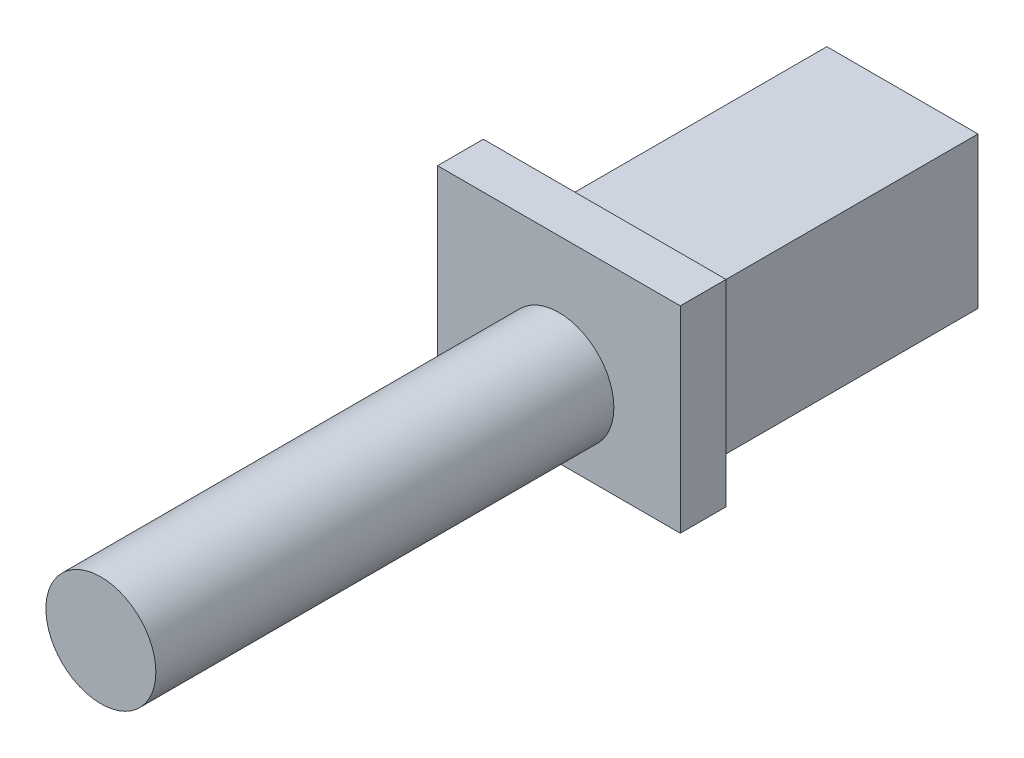
SolidWorks part; units mm, degrees
ref_plane "Front" through (0, 0, 0) normal (0, 0, 1) x (1, 0, 0)
ref_plane "Top" through (0, 0, 0) normal (0, 1, 0) x (1, 0, 0)
ref_plane "Right" through (0, 0, 0) normal (1, 0, 0) x (0, 0, -1)
sketch "Sketch3" plane through (0, 0, 0) normal (0, 0, 1) x (1, 0, 0)
  line L0 (-3.3, -3.3) -> (-5.3, -3.3)
  line L1 (-3.3, 3.3) -> (3.3, 3.3)
  line L2 (-3.3, 3.3) -> (-3.3, -3.3)
  line L3 (-3.3, -3.3) -> (3.3, -3.3)
  line L4 (3.3, 3.3) -> (3.3, -3.3)
  line L5 (-3.3, 3.3) -> (3.3, -3.3) construction
  line L6 (-3.3, -3.3) -> (3.3, 3.3) construction
  line L7 (-5.3, -3.3) -> (-5.3, 5.3)
  line L8 (-5.3, 5.3) -> (5.3, 5.3)
  line L9 (5.3, 5.3) -> (5.3, -3.3)
  line L10 (3.3, -3.3) -> (5.3, -3.3)
  circle A0 centre (0, 0) radius 2.4
  point P0 (0, 0)
  dimension "D2" = 4.8
  dimension "D1" = 6.6
  dimension "D3" = 2
  dimension "D4" = 2
  dimension "D5" = 2
extrude "Boss-Extrude1" add sketch "Sketch3" along normal blind 20 contours A0
extrude "Boss-Extrude2" add sketch "Sketch3<4>" against normal blind 15 contours L4 L1 L2 L3 A0 | A0 region at (-3.2067, 0, 0) region at (0, 0, 0)
sketch "Sketch3<4>" plane through (0, 0, 0) normal (0, 0, 1) x (1, 0, 0) same geometry as "Sketch3"
extrude "Boss-Extrude3" add sketch "Sketch3<5>" against normal blind 2 contours L4 L10 L9 L8 L7 L0 L2 L1 region at (-4.3, -3.1635, 0)
sketch "Sketch3<5>" plane through (0, 0, 0) normal (0, 0, 1) x (1, 0, 0) same geometry as "Sketch3"
